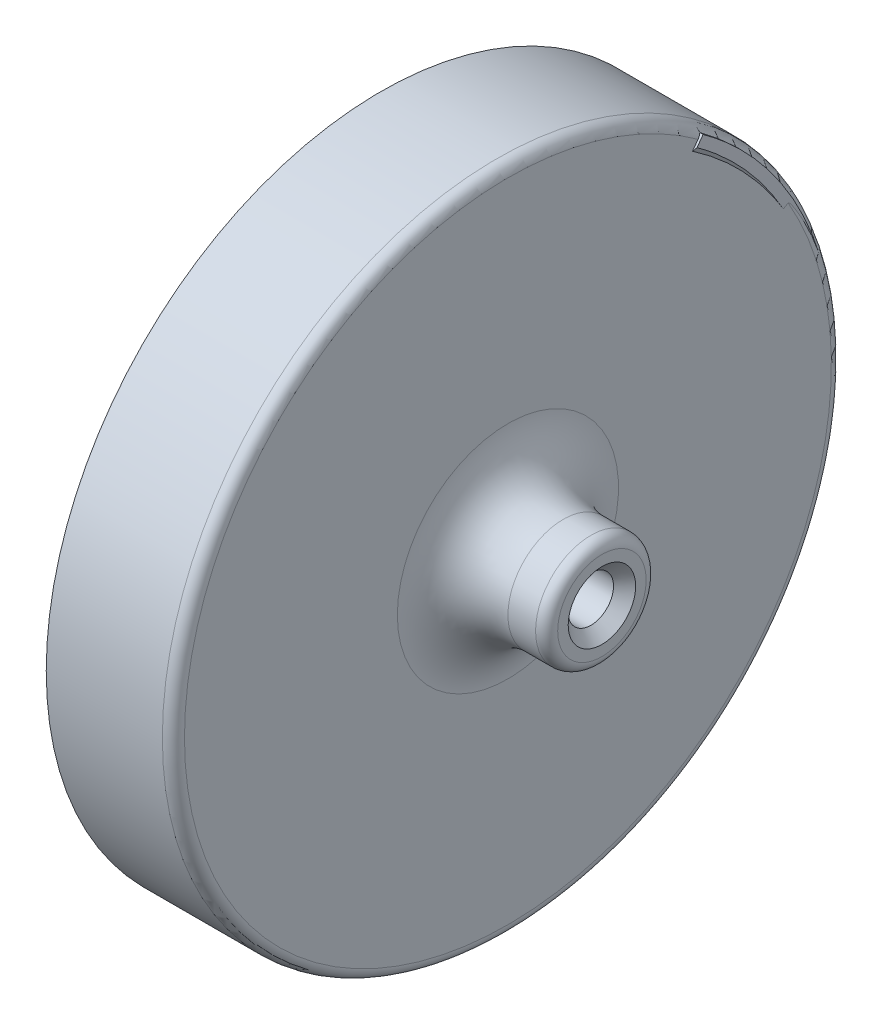
SolidWorks part; units mm, degrees
note: '?' marks a value the reader was unsure of.
ref_plane "Front" through (0, 0, 0) normal (0, 0, 1) x (1, 0, 0)
ref_plane "Top" through (0, 0, 0) normal (0, 1, 0) x (1, 0, 0)
ref_plane "Side" through (0, 0, 0) normal (1, 0, 0) x (0, 0, -1)
ref_axis "X_Axis" through (-20.1896, 0, 0) along (1, 0, 0)?
ref_axis "Y_Axis" through (0, -14.8261, 0) along (0, 1, 0)?
ref_axis "Z_Axis" through (0, 0, -19.842) along (0, 0, 1)?
sketch "Sketch1" plane through (0, 0, 0) normal (0, 0, 1) x (1, 0, 0)
  line L0 (0, 60.5) -> (21, 60.5)
  line L1 (23, 58.5) -> (23, 20)
  line L3 (20, 6.1) -> (20, 55.5)
  line L4 (18, 57.5) -> (0, 57.5)
  line L5 (0, 57.5) -> (0, 60.5)
  line L6 (0, 0) -> (57.066, 0) construction
  line L7 (22, 4.1) -> (38, 4.1)
  line L8 (40, 6.1) -> (40, 8)
  line L9 (38, 10) -> (33, 10)
  line L10 (38, 4.1) -> (40, 6.1)
  line L11 (20, 6.1) -> (22, 4.1)
  arc A0 (23, 20) -> (33, 10) centre (33, 20) ccw
  arc A1 (20, 55.5) -> (18, 57.5) centre (18, 55.5) ccw
  arc A2 (21, 60.5) -> (23, 58.5) centre (21, 58.5) cw
  arc A3 (40, 8) -> (38, 10) centre (38, 8) ccw
  point P4 (20, 4.1)
  point P9 (0, 0)
  point P11 (40, 4.1)
  point P20 (20, 57.5)
  dimension "D8" = 10
  dimension "D9" = 2
  dimension "D1" = 115
  dimension "D2" = 121
  dimension "D3" = 8.2
  dimension "D4" = 20
  dimension "D5" = 20
  dimension "D6" = 3
  dimension "D7" = 20
revolve "Revolve1" add sketch "Sketch1" angle 360 about L6
sketch "Sketch2" plane through (0, 0, 0) normal (-1, 0, 0) x (0, 0, 1)
  circle A0 centre (0, 0) radius 57.5 construction
  circle A1 centre (0, 0) radius 57.5
curve "Helix/Spiral1" pitch 6 height 26.4 turns 4.4
sketch "Sketch3" plane through (0, 0, 0) normal (0, 0, 1) x (1, 0, 0)
  line L0 (0, 57.5) -> (-2.1494, 53.7771)
  line L1 (-3.6506, 53.7771) -> (-5.8, 57.5)
  line L2 (-5.8, 57.5) -> (-5.8, 59.3656)
  line L3 (-5.8, 59.3656) -> (0, 59.3656)
  line L4 (0, 60.5) -> (0, -60.5) construction
  line L5 (0, 59.3656) -> (0, 57.5)
  line L6 (-2.9, 52.4771) -> (-2.9, 59.3656) construction
  line L7 (-3.6506, 53.7771) -> (-2.1494, 53.7771)
  point P3 (-3.7572, 53.7771)
  point P12 (-2.9, 53.7771)
  dimension "D1" = 60
  dimension "D2" = 5.8
  dimension "D3" = 1.3
  dimension "D4" = 3.7229
sweep "Sweep1" add profiles "Sketch3" path "Helix/Spiral1"
sketch "Sketch4" plane through (0, 0, 0) normal (-1, 0, 0) x (0, 0, 1)
  circle A0 centre (0, 0) radius 60.5
extrude "Cut-Extrude1" cut sketch "Sketch4" along normal through all
